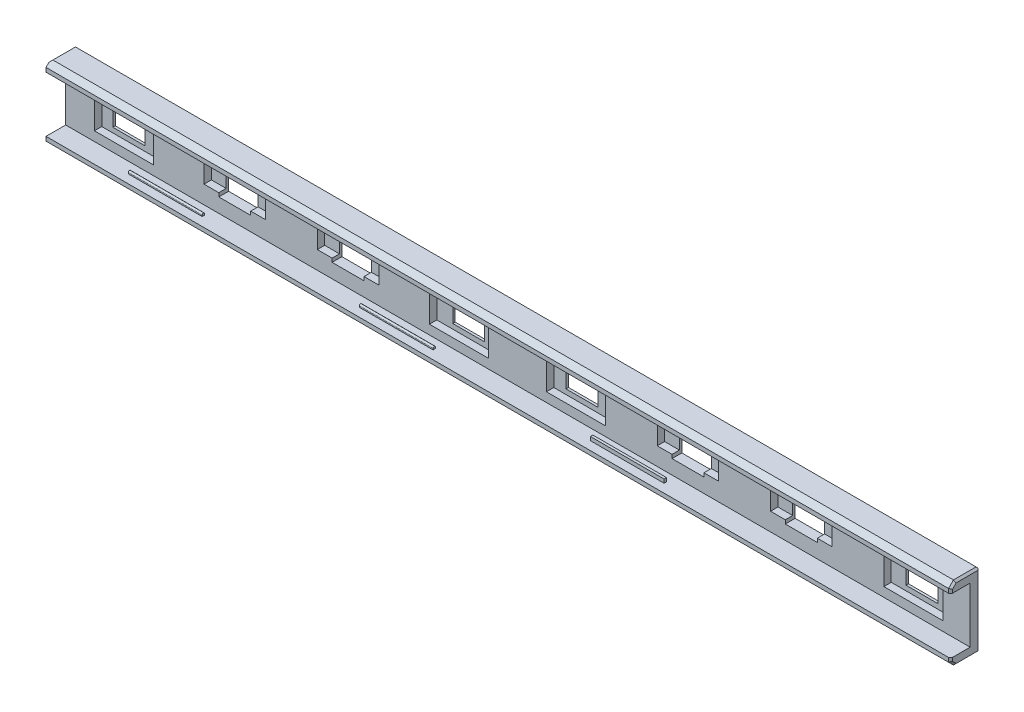
SolidWorks part; units mm, degrees
ref_plane "Front Plane" through (0, 0, 0) normal (0, 0, 1) x (1, 0, 0)
ref_plane "Top Plane" through (0, 0, 0) normal (0, 1, 0) x (1, 0, 0)
ref_plane "Right Plane" through (0, 0, 0) normal (1, 0, 0) x (0, 0, -1)
sketch "Sketch1" plane through (0, 0, 0) normal (0, 0, 1) x (1, 0, 0)
  line L1 (-137.75, 25.6543) -> (46.25, 25.6543)
  line L2 (-137.75, 25.6543) -> (-137.75, 10.6543)
  line L3 (-137.75, 10.6543) -> (46.25, 10.6543)
  line L4 (46.25, 25.6543) -> (46.25, 10.6543)
  dimension "D1" = 184
  dimension "D2" = 15
extrude "Boss-Extrude1" add sketch "Sketch1" along normal blind 6
sketch "Sketch2" plane through (0, 0, 6) normal (0, 0, 1) x (1, 0, 0)
  line L0 (-137.75, 25.6543) -> (-137.75, 10.6543) construction
  line L1 (-129.65, 20.9043) -> (-123.15, 20.9043)
  line L2 (-129.65, 20.9043) -> (-129.65, 15.4043)
  line L3 (-129.65, 15.4043) -> (-123.15, 15.4043)
  line L4 (-123.15, 20.9043) -> (-123.15, 15.4043)
  line L5 (46.25, 25.6543) -> (-137.75, 25.6543) construction
  dimension "D1" = 6.5
  dimension "D2" = 5.5
  dimension "D3" = 8.1
  dimension "D4" = 4.75
extrude "Cut-Extrude1" cut sketch "Sketch2" against normal through all both and the other way through all
sketch "Sketch3" plane through (0, 0, 6) normal (0, 0, 1) x (1, 0, 0)
  line L0 (-123.15, 15.4043) -> (-123.15, 20.9043) construction
  line L1 (-106.6, 20.9043) -> (-100.1, 20.9043)
  line L2 (-106.6, 20.9043) -> (-106.6, 15.4043)
  line L3 (-106.6, 15.4043) -> (-100.1, 15.4043)
  line L4 (-100.1, 20.9043) -> (-100.1, 15.4043)
  dimension "D1" = 6.5
  dimension "D2" = 5.5
  dimension "D3" = 16.55
extrude "Cut-Extrude2" cut sketch "Sketch3" against normal through all both and the other way through all
sketch "Sketch4" plane through (0, 0, 6) normal (0, 0, 1) x (1, 0, 0)
  line L0 (-100.1, 15.4043) -> (-100.1, 20.9043) construction
  line L1 (-83.55, 20.9043) -> (-77.05, 20.9043)
  line L2 (-83.55, 20.9043) -> (-83.55, 15.4043)
  line L3 (-83.55, 15.4043) -> (-77.05, 15.4043)
  line L4 (-77.05, 20.9043) -> (-77.05, 15.4043)
  line L5 (-137.75, 10.6543) -> (46.25, 10.6543) construction
  dimension "D1" = 6.5
  dimension "D2" = 5.5
  dimension "D3" = 16.55
  dimension "D4" = 4.75
extrude "Cut-Extrude3" cut sketch "Sketch4" against normal through all both and the other way through all
sketch "Sketch5" plane through (0, 0, 6) normal (0, 0, 1) x (1, 0, 0)
  line L0 (-77.05, 15.4043) -> (-77.05, 20.9043) construction
  line L1 (-60.5, 20.9043) -> (-54, 20.9043)
  line L2 (-60.5, 20.9043) -> (-60.5, 15.4043)
  line L3 (-60.5, 15.4043) -> (-54, 15.4043)
  line L4 (-54, 20.9043) -> (-54, 15.4043)
  line L6 (-37.45, 20.9043) -> (-30.95, 20.9043)
  line L7 (-37.45, 20.9043) -> (-37.45, 15.4043)
  line L8 (-37.45, 15.4043) -> (-30.95, 15.4043)
  line L9 (-30.95, 20.9043) -> (-30.95, 15.4043)
  line L10 (-14.4, 20.9043) -> (-7.9, 20.9043)
  line L11 (-14.4, 20.9043) -> (-14.4, 15.4043)
  line L12 (-14.4, 15.4043) -> (-7.9, 15.4043)
  line L13 (-7.9, 20.9043) -> (-7.9, 15.4043)
  line L14 (8.65, 20.9043) -> (15.15, 20.9043)
  line L15 (8.65, 20.9043) -> (8.65, 15.4043)
  line L16 (8.65, 15.4043) -> (15.15, 15.4043)
  line L17 (15.15, 20.9043) -> (15.15, 15.4043)
  line L18 (31.7, 20.9043) -> (38.2, 20.9043)
  line L19 (31.7, 20.9043) -> (31.7, 15.4043)
  line L20 (31.7, 15.4043) -> (38.2, 15.4043)
  line L21 (38.2, 20.9043) -> (38.2, 15.4043)
  dimension "D1" = 6.5
  dimension "D2" = 5.5
  dimension "D3" = 16.55
  dimension "D4" = 6.5
  dimension "D5" = 6.5
  dimension "D6" = 5.5
  dimension "D7" = 5.5
  dimension "D8" = 16.55
  dimension "D9" = 16.55
  dimension "D10" = 6.5
  dimension "D11" = 6.5
  dimension "D12" = 5.5
  dimension "D13" = 5.5
  dimension "D14" = 16.55
  dimension "D15" = 16.55
extrude "Cut-Extrude4" cut sketch "Sketch5" against normal through all both and the other way through all
sketch "Sketch8" plane through (0, 0, 6) normal (0, 0, 1) x (1, 0, 0)
  line L0 (-137.75, 25.6543) -> (-137.75, 10.6543) construction
  line L1 (46.25, 10.6543) -> (46.25, 25.6543) construction
  line L2 (-137.75, 23.8043) -> (46.25, 23.8043)
  line L3 (-137.75, 23.8043) -> (-137.75, 12.5043)
  line L4 (-137.75, 12.5043) -> (46.25, 12.5043)
  line L5 (46.25, 23.8043) -> (46.25, 12.5043)
  line L6 (46.25, 25.6543) -> (-137.75, 25.6543) construction
  dimension "D1" = 11.3
  dimension "D2" = 1.85
extrude "Cut-Extrude5" cut sketch "Sketch8" against normal blind 4 and the other way through all
sketch "Sketch9" plane through (0, 0, 2) normal (0, 0, 1) x (1, 0, 0)
  line L0 (-7.9, 15.4043) -> (-14.4, 15.4043) construction
  line L1 (-54, 20.9043) -> (-54, 15.4043) construction
  line L2 (-7.9, 20.9043) -> (-7.9, 15.4043) construction
  line L3 (-63.75, 21.9043) -> (-51.75, 21.9043)
  line L4 (-63.75, 21.9043) -> (-63.75, 14.4043)
  line L5 (-63.75, 14.4043) -> (-51.75, 14.4043)
  line L6 (-51.75, 21.9043) -> (-51.75, 14.4043)
  line L7 (-137.75, 12.5043) -> (46.25, 12.5043) construction
  line L8 (-37.45, 15.4043) -> (-37.45, 20.9043) construction
  line L9 (-39.95, 21.9043) -> (-27.95, 21.9043)
  line L10 (-39.95, 21.9043) -> (-39.95, 14.4043)
  line L11 (46.25, 12.5043) -> (-137.75, 12.5043) construction
  line L12 (-131.9, 21.9043) -> (-119.9, 21.9043)
  line L13 (-131.9, 21.9043) -> (-131.9, 14.4043)
  line L14 (-131.9, 14.4043) -> (-119.9, 14.4043)
  line L15 (-119.9, 21.9043) -> (-119.9, 14.4043)
  line L16 (-129.65, 15.4043) -> (-129.65, 20.9043) construction
  line L17 (-39.95, 14.4043) -> (-27.95, 14.4043)
  line L18 (-27.95, 21.9043) -> (-27.95, 14.4043)
  line L20 (-4.9, 20.1543) -> (-17.4, 20.1543)
  line L21 (-4.9, 20.1543) -> (-4.9, 16.1543)
  line L22 (-4.9, 16.1543) -> (-17.4, 16.1543)
  line L23 (-17.4, 20.1543) -> (-17.4, 16.1543)
  line L24 (15.15, 20.9043) -> (15.15, 15.4043) construction
  line L25 (5.65, 20.1543) -> (18.15, 20.1543)
  line L26 (5.65, 20.1543) -> (5.65, 16.1543)
  line L27 (5.65, 16.1543) -> (18.15, 16.1543)
  line L28 (18.15, 20.1543) -> (18.15, 16.1543)
  line L29 (38.2, 20.9043) -> (38.2, 15.4043) construction
  line L30 (28.7, 21.9043) -> (40.7, 21.9043)
  line L31 (28.7, 21.9043) -> (28.7, 14.4043)
  line L32 (28.7, 14.4043) -> (40.7, 14.4043)
  line L33 (40.7, 21.9043) -> (40.7, 14.4043)
  dimension "D1" = 2.25
  dimension "D2" = 12
  dimension "D3" = 7.5
  dimension "D4" = 1.9
  dimension "D5" = 12
  dimension "D6" = 7.5
  dimension "D7" = 1.9
  dimension "D8" = 2.25
  dimension "D9" = 12
  dimension "D10" = 2.5
  dimension "D11" = 7.5
  dimension "D12" = 4
  dimension "D13" = 12.5
  dimension "D14" = 0.75
  dimension "D15" = 3
  dimension "D16" = 12.5
  dimension "D17" = 3
  dimension "D18" = 12
  dimension "D19" = 7.5
  dimension "D20" = 2.5
extrude "Cut-Extrude6" cut sketch "Sketch9" against normal blind 1.5
sketch "Sketch10" plane through (0, 0, 2) normal (0, 0, 1) x (1, 0, 0)
  line L1 (-86.55, 20.1543) -> (-74.05, 20.1543)
  line L2 (-86.55, 20.1543) -> (-86.55, 16.1543)
  line L3 (-86.55, 16.1543) -> (-74.05, 16.1543)
  line L4 (-74.05, 20.1543) -> (-74.05, 16.1543)
  line L5 (-109.6, 20.1543) -> (-97.1, 20.1543)
  line L6 (-109.6, 20.1543) -> (-109.6, 16.1543)
  line L7 (-109.6, 16.1543) -> (-97.1, 16.1543)
  line L8 (-97.1, 20.1543) -> (-97.1, 16.1543)
  line L9 (-106.6, 15.4043) -> (-106.6, 20.9043) construction
  line L10 (-100.1, 20.9043) -> (-100.1, 15.4043) construction
  line L11 (-100.1, 15.4043) -> (-106.6, 15.4043) construction
  line L13 (-83.55, 15.4043) -> (-83.55, 20.9043) construction
  line L15 (-77.05, 15.4043) -> (-83.55, 15.4043) construction
  dimension "D1" = 3
  dimension "D2" = 3
  dimension "D3" = 4
  dimension "D4" = 0.75
  dimension "D5" = 12.5
  dimension "D6" = 3
  dimension "D7" = 4
  dimension "D8" = 0.75
extrude "Cut-Extrude7" cut sketch "Sketch10" against normal blind 1.5
sketch "Sketch12" plane through (46.25, 0, 0) normal (1, 0, 0) x (0, 0, -1)
  line L0 (-6, 25.6543) -> (-6, 24.6543)
  line L1 (-6, 23.8043) -> (-6, 25.6543) construction
  line L2 (-6, 24.6543) -> (-5, 25.6543)
  line L3 (-6, 25.6543) -> (0, 25.6543) construction
  line L4 (-5, 25.6543) -> (-6, 25.6543)
  line L5 (-6, 10.6543) -> (-5, 10.6543)
  line L6 (-6, 10.6543) -> (0, 10.6543) construction
  line L7 (-5, 10.6543) -> (-6, 11.6543)
  line L8 (-6, 10.6543) -> (-6, 12.5043) construction
  line L9 (-6, 11.6543) -> (-6, 10.6543)
  dimension "D1" = 1
  dimension "D2" = 1
  dimension "D3" = 1
extrude "Cut-Extrude8" cut sketch "Sketch12" against normal up to surface (184 mm away) up to face at (-137.75, 18.1543, 3.5)
sketch "Sketch13" plane through (0, 0, 0) normal (0, 0, -1) x (-1, 0, 0)
  line L0 (137.75, 25.6543) -> (137.75, 10.6543) construction
  line L1 (135.25, 23.1543) -> (135.75, 23.1543)
  line L2 (135.25, 23.1543) -> (135.25, 13.1543)
  line L3 (135.25, 13.1543) -> (135.75, 13.1543)
  line L4 (135.75, 23.1543) -> (135.75, 13.1543)
  line L5 (-46.25, 25.6543) -> (137.75, 25.6543) construction
  dimension "D1" = 2
  dimension "D2" = 0.5
  dimension "D3" = 10
  dimension "D4" = 2.5
extrude "Cut-Extrude9" cut sketch "Sketch13" against normal blind 0.6
fillet "Fillet1" radius 0.25 1 edges at (-135.75, 18.1543, 0)
fillet "Fillet2" radius 0.25 4 edges at (-135.5, 23.1543, 0.6) (-135.75, 18.1543, 0.6) (-135.5, 13.1543, 0.6) (-135.25, 18.1543, 0.6)
sketch "Sketch16" plane through (0, 23.8043, 0) normal (0, -1, 0) x (1, 0, 0)
  line L0 (-137.75, 6) -> (46.25, 6) construction
  line L1 (-107.75, 4.25) -> (-122.75, 4.25)
  line L2 (-107.75, 4.25) -> (-107.75, 3.75)
  line L3 (-107.75, 3.75) -> (-122.75, 3.75)
  line L4 (-122.75, 4.25) -> (-122.75, 3.75)
  line L5 (-137.75, 6) -> (-137.75, 2) construction
  dimension "D1" = 15
  dimension "D2" = 0.5
  dimension "D3" = 1.75
  dimension "D4" = 15
extrude "Boss-Extrude2" add sketch "Sketch16" along normal blind 0.75
fillet "Fillet3" radius 0.5 1 edges at (-115.25, 23.0543, 4.25)
fillet "Fillet4" radius 0.25 1 edges at (-115.25, 23.0543, 3.75)
sketch "Sketch17" plane through (0, 12.5043, 0) normal (0, 1, 0) x (1, 0, 0)
  line L0 (-137.75, -6) -> (-137.75, -2) construction
  line L1 (-107.75, -3.75) -> (-122.75, -3.75)
  line L2 (-107.75, -3.75) -> (-107.75, -4.25)
  line L3 (-107.75, -4.25) -> (-122.75, -4.25)
  line L4 (-122.75, -3.75) -> (-122.75, -4.25)
  line L5 (46.25, -6) -> (-137.75, -6) construction
  dimension "D1" = 15
  dimension "D2" = 0.5
  dimension "D3" = 15
  dimension "D4" = 1.75
extrude "Boss-Extrude3" add sketch "Sketch17" along normal blind 0.75
fillet "Fillet5" radius 0.5 1 edges at (-115.25, 13.2543, 4.25)
fillet "Fillet6" radius 0.25 1 edges at (-115.25, 13.2543, 3.75)
pattern_linear "LPattern1" count 3 spacing 47 along (1, 0, 0) of "Boss-Extrude3"
pattern_linear "LPattern2" count 3 spacing 47 along (1, 0, 0) of "Boss-Extrude2"
fillet "Fillet7" radius 0.5 1 edges at (-68.25, 23.0543, 4.25)
fillet "Fillet8" radius 0.25 1 edges at (-68.25, 23.0543, 3.75)
fillet "Fillet9" radius 0.5 1 edges at (-68.25, 13.2543, 4.25)
fillet "Fillet10" radius 0.25 1 edges at (-68.25, 13.2543, 3.75)
chamfer "Chamfer1" distance 0.4 angle 45 2 edges at (-45.75, 10.6543, 0) (-45.75, 25.6543, 0)
chamfer "Chamfer2" distance 0.4 angle 45 2 edges at (46.25, 18.1543, 0) (-137.75, 18.1543, 0)
chamfer "Chamfer3" distance 0.4 angle 45 2 edges at (-137.75, 10.6543, 2.7) (-137.75, 25.6543, 2.7)
chamfer "Chamfer5" distance 0.4 angle 45 6 edges at (46.25, 24.2293, 6) (46.25, 25.1543, 5.5) (46.25, 25.6543, 2.7) (46.25, 12.0793, 6) (46.25, 11.1543, 5.5) (46.25, 10.6543, 2.7)
